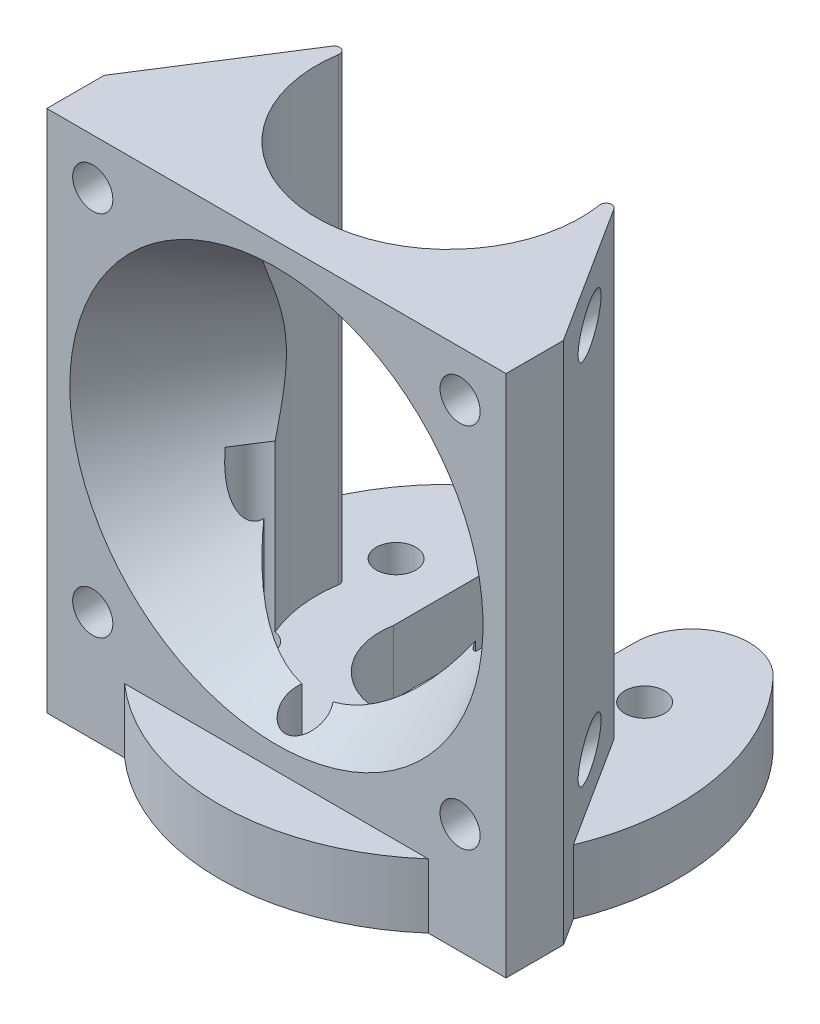
SolidWorks part; units mm, degrees
ref_plane "Front Plane" through (0, 0, 0) normal (0, 0, 1) x (1, 0, 0)
ref_plane "Top Plane" through (0, 0, 0) normal (0, 1, 0) x (1, 0, 0)
ref_plane "Right Plane" through (0, 0, 0) normal (1, 0, 0) x (0, 0, -1)
sketch "Sketch1" plane through (0, 0, 0) normal (0, 1, 0) x (1, 0, 0)
  circle A0 centre (0, 0) radius 20
  circle A1 centre (0, 0) radius 6
  dimension "D1" = 40
  dimension "D2" = 12
extrude "Boss-Extrude1" add sketch "Sketch1" along normal blind 5.6
sketch "Sketch2" plane through (0, 5.6, 0) normal (0, 1, 0) x (1, 0, 0)
  line L0 (-5.9, 1.0909) -> (-5.9, 19.1099)
  line L1 (5.9, 1.0909) -> (5.9, 19.1099)
  arc A0 (5.9, 1.0909) -> (-5.9, 1.0909) centre (0, 0) ccw
  arc A1 (5.9, 19.1099) -> (-5.9, 19.1099) centre (0, 0) ccw
  circle A2 centre (0, 0) radius 20 construction
  circle A3 centre (0, 0) radius 6 construction
  dimension "D1" = 11.8
extrude "Cut-Extrude1" cut sketch "Sketch2" against normal through all
fillet "Fillet1" radius 5 2 edges at (5.9, 2.8, -19.1099) (-5.9, 2.8, -19.1099)
sketch "Sketch3" plane through (0, 5.6, 0) normal (0, 1, 0) x (1, 0, 0)
  line L0 (-20, -15) -> (20, -15)
  line L1 (20, -15) -> (20, -10)
  line L2 (20, -10) -> (9.7007, 6.1763)
  line L4 (-9.7007, 6.1763) -> (-20, -10)
  line L5 (-20, -10) -> (-20, -15)
  line L6 (0, -15) -> (0, 0) construction
  arc A0 (-9.7007, 6.1763) -> (9.7007, 6.1763) centre (0, 0) ccw
  circle A2 centre (0, 0) radius 25 construction
  dimension "D1" = 40
  dimension "D2" = 23
  dimension "D3" = 50
  dimension "D4" = 5
extrude "Boss-Extrude2" add sketch "Sketch3" along normal blind 40
sketch "Sketch4" plane through (0, 0, 0) normal (0, -1, 0) x (1, 0, 0)
  line L0 (13.2288, 15) -> (20, 15)
  line L1 (20, 15) -> (20, 10)
  line L2 (20, 10) -> (18.4888, 7.6265)
  line L3 (0, 0) -> (0, 20) construction
  line L4 (-20, 10) -> (-18.4888, 7.6265)
  line L5 (-20, 15) -> (-20, 10)
  line L6 (-13.2288, 15) -> (-20, 15)
  arc A0 (18.4888, 7.6265) -> (13.2288, 15) centre (0, 0) ccw
  arc A1 (14.5333, -13.7398) -> (-14.5333, -13.7398) centre (0, 0) ccw construction
  arc A2 (-18.4888, 7.6265) -> (-13.2288, 15) centre (0, 0) cw
extrude "Boss-Extrude3" add sketch "Sketch4" against normal up to next
fillet "Fillet2" radius 0.5 2 edges at (-9.7007, 25.6, -6.1763) (9.7007, 25.6, -6.1763)
ref_plane "Plane1" through (0, 25.6, 0) normal (0, 1, 0) x (1, 0, 0)
sketch "Sketch5" plane through (0, 25.6, 0) normal (0, 1, 0) x (1, 0, 0)
  line L0 (0, 0) -> (0, -15) construction
  line L1 (-20, -15) -> (20, -15) construction
  line L2 (0, -15) -> (18, -15)
  line L3 (18, -15) -> (11.0922, -3.0353)
  line L4 (11.0922, -3.0353) -> (0, -3.0353)
  line L5 (0, -3.0353) -> (0, -15)
  arc A0 (-11.3607, 1.7847) -> (11.3607, 1.7847) centre (0, 0) ccw construction
  dimension "D1" = 18
  dimension "D2" = 60
revolve "Cut-Revolve1" cut sketch "Sketch5" angle 360 about L0
sketch "Sketch6" plane through (0, 0, 15) normal (0, 0, 1) x (1, 0, 0)
  line L1 (-20, 45.6) -> (20, 45.6) construction
  line L3 (20, 45.6) -> (20, 0) construction
  circle A0 centre (-16, 9.6) radius 1.75
  circle A1 centre (16, 9.6) radius 1.75
  circle A2 centre (16, 41.6) radius 1.75
  circle A3 centre (-16, 41.6) radius 1.75
  dimension "D1" = 3.5
  dimension "D2" = 16
  dimension "D5" = 4
  dimension "D6" = 4
  dimension "D7" = 32
  dimension "D3" = 2
  dimension "D4" = 2
extrude "Cut-Extrude2" cut sketch "Sketch6" against normal through all
sketch "Sketch7" plane through (0, 0, 0) normal (0, -1, 0) x (1, 0, 0)
  circle A0 centre (0, 0) radius 12.5 construction
  circle A1 centre (0, 12.5) radius 1.725
  circle A2 centre (10.8253, 6.25) radius 1.725
  circle A3 centre (10.8253, -6.25) radius 1.725
  circle A4 centre (0, -12.5) radius 1.725
  circle A5 centre (-10.8253, -6.25) radius 1.725
  circle A6 centre (-10.8253, 6.25) radius 1.725
  point P17 (0, 0)
  dimension "D1" = 25
  dimension "D2" = 3.45
extrude "Cut-Extrude4" cut sketch "Sketch7" against normal blind 20
